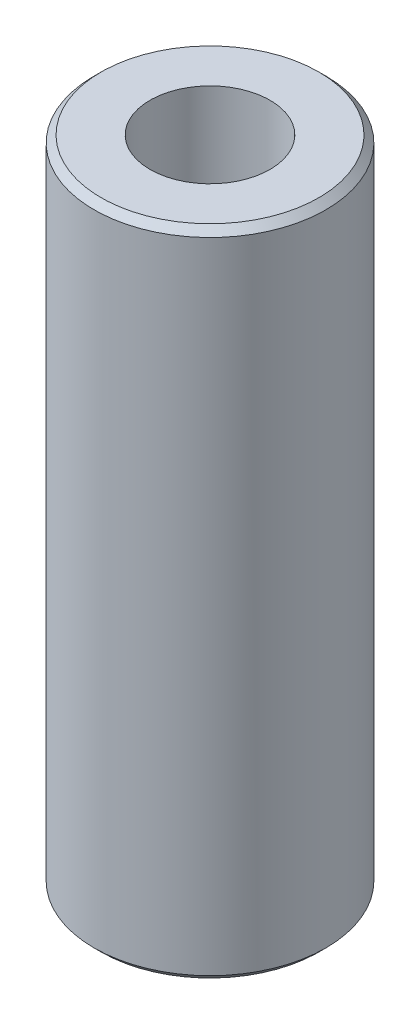
SolidWorks part; units mm, degrees
ref_plane "Front Plane" through (0, 0, 0) normal (0, 0, 1) x (1, 0, 0)
ref_plane "Top Plane" through (0, 0, 0) normal (0, 1, 0) x (1, 0, 0)
ref_plane "Right Plane" through (0, 0, 0) normal (1, 0, 0) x (0, 0, -1)
sketch "Sketch1" plane through (0, 0, 0) normal (0, 1, 0) x (1, 0, 0)
  circle A0 centre (0, 0) radius 52.5
  dimension "SHAFT_OD" = 105
extrude "Boss-Extrude1" add sketch "Sketch1" along normal blind 295.9422
sketch "Sketch2" plane through (0, 0, 0) normal (0, 1, 0) x (1, 0, 0)
  circle A0 centre (0, 0) radius 27.1837
  dimension "BORE_D" = 54.3674
extrude "Cut-Extrude1" cut sketch "Sketch2" along normal through all
chamfer "Chamfer1" distance 3.1668 angle 45 2 edges at (0, 295.9422, 52.5) (0, 0, 52.5)
